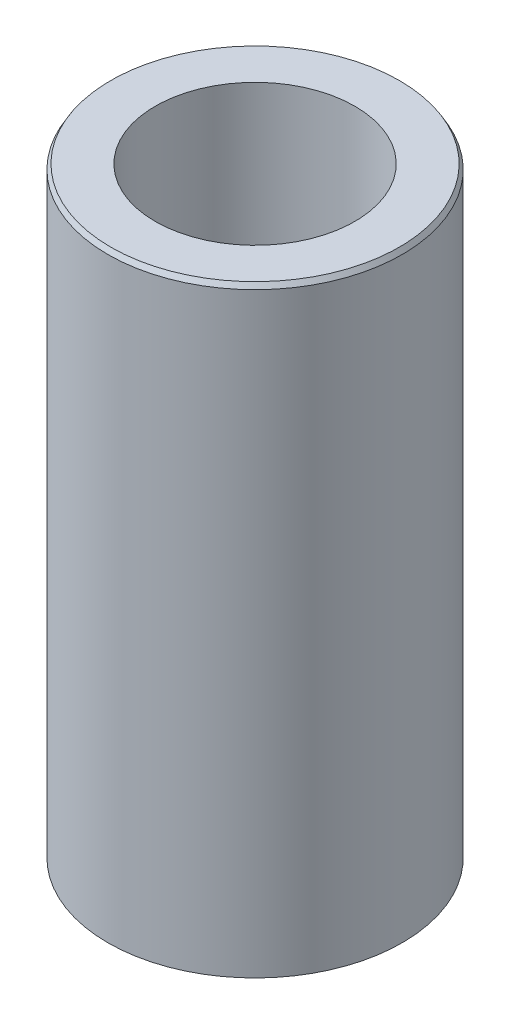
SolidWorks part; units mm, degrees
ref_plane "Front Plane" through (0, 0, 0) normal (0, 0, 1) x (1, 0, 0)
ref_plane "Top Plane" through (0, 0, 0) normal (0, 1, 0) x (1, 0, 0)
ref_plane "Right Plane" through (0, 0, 0) normal (1, 0, 0) x (0, 0, -1)
sketch "Sketch1" plane through (0, 0, 0) normal (0, 1, 0) x (1, 0, 0)
  circle A0 centre (0, 0) radius 35
  dimension "SHAFT_OD" = 70
extrude "Boss-Extrude1" add sketch "Sketch1" along normal blind 143.5954
sketch "Sketch2" plane through (0, 0, 0) normal (0, 1, 0) x (1, 0, 0)
  circle A0 centre (0, 0) radius 23.7404
  dimension "BORE_D" = 47.4808
extrude "Cut-Extrude1" cut sketch "Sketch2" along normal through all
chamfer "Chamfer1" distance 1.1767 angle 30 2 edges at (0, 143.5954, 35) (0, 0, 35) first distance on face at (0, 143.5954, 35) first distance on face at (0, 0, 23.7404)
